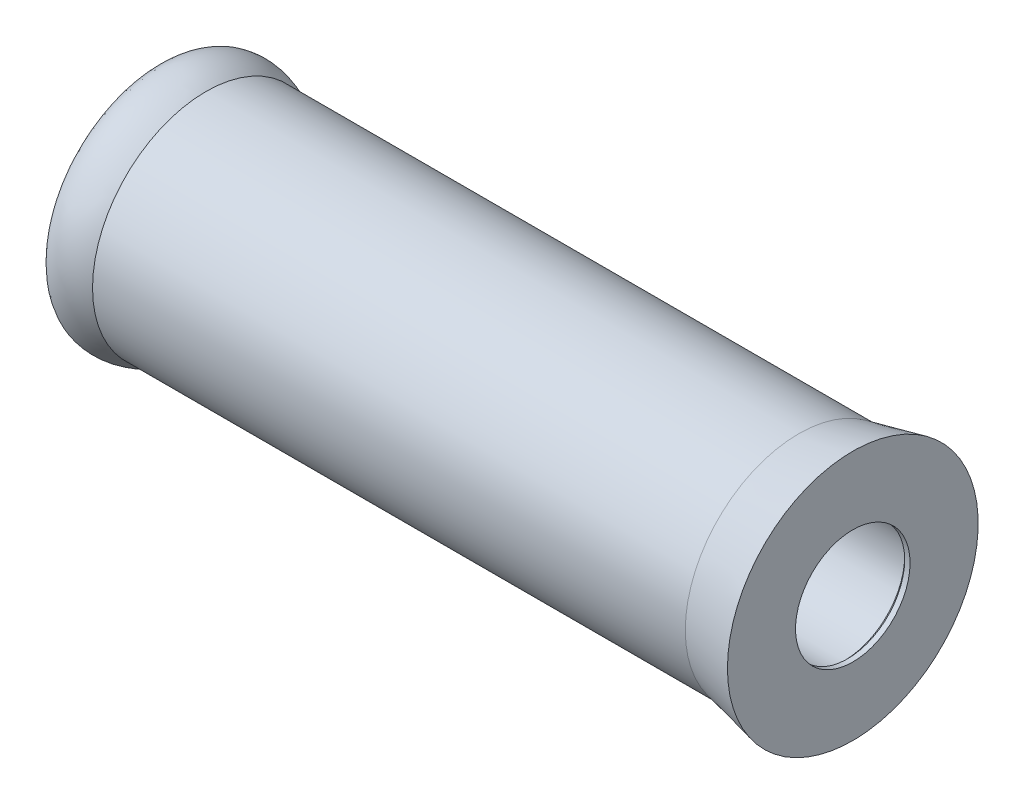
SolidWorks part; units mm, degrees
ref_plane "Front Plane" through (0, 0, 0) normal (0, 0, 1) x (1, 0, 0)
ref_plane "Top Plane" through (0, 0, 0) normal (0, 1, 0) x (1, 0, 0)
ref_plane "Right Plane" through (0, 0, 0) normal (1, 0, 0) x (0, 0, -1)
sketch "Sketch1" plane through (0, 0, 0) normal (1, 0, 0) x (0, 0, -1)
  circle A0 centre (0, 0) radius 11.2
  circle A1 centre (0, 0) radius 13.5
  dimension "D1" = 22.4
  dimension "D2" = 27
extrude "Boss-Extrude1" add sketch "Sketch1" along normal blind 60
ref_axis "Axis1" through (0, 0, 0) along (1, 0, 0)
sketch "Sketch2" plane through (0, 0, 0) normal (0, 0, 1) x (1, 0, 0)
  line L0 (8, 12.6) -> (8, 9.6)
  line L1 (8, 9.6) -> (11, 9.6)
  line L2 (0, 13.5) -> (0, -13.5) construction
  arc A0 (8, 12.6) -> (11, 9.6) centre (8, 9.6) cw
  dimension "D1" = 3
  dimension "D2" = 12.6
  dimension "D3" = 8
revolve "Cut-Revolve1" cut sketch "Sketch2" angle 360 about L0
pattern_circular "CirPattern1" count 8 over 360 about axis through (60, 0, 0) along (-1, 0, 0) of "Cut-Revolve1" reverse direction yes
pattern_linear "LPattern1" count 3 spacing 20 along (1, 0, 0) of "CirPattern1"
fillet "Fillet1" radius 3 1 edges at (0, 0, -11.2)
sketch "Sketch3" plane through (0, 0, 0) normal (0, 0, 1) x (1, 0, 0)
  line L0 (0, 0) -> (130, 0) construction
  line L1 (10.3, 21) -> (120, 21)
  line L2 (120, 21) -> (130, 23.2)
  line L3 (130, 23.2) -> (130, 11.2)
  line L5 (130, 11.2) -> (60, 11.2)
  line L7 (60, 11.2) -> (60, 13.5)
  line L8 (60, 13.5) -> (0, 13.5)
  line L9 (31.8374, 8.5654) -> (-11.2374, 33.4346) construction
  line L10 (15.8707, 28.0017) -> (-9.1636, 16.328) construction
  line L11 (60, -13.5) -> (60, 13.5) construction
  line L12 (60, -11.2) -> (60, 11.2) construction
  line L13 (60, 11.2) -> (50.5377, 11.2) construction
  line L14 (0, 16.8301) -> (0, 10.1693) construction
  line L15 (0, 13.5) -> (0, -13.5) construction
  spline S0 degree 3 poles (0, 13.5) (0, 17.4) (0.7244, 20.8873) (4.5323, 22.7857) (7.7019, 22.5) (10.3, 21) knots 0 0 0 0 0.520343 0.620343 1 1 1 1
  point P19 (60, 11.2)
  dimension "D5" = 30
  dimension "D6" = 10
  dimension "D7" = 25
  dimension "D8" = 13
  dimension "D9" = 13
  dimension "D1" = 21
  dimension "D2" = 130
  dimension "D3" = 22
  dimension "D4" = 10.3
  dimension "D10" = 3
  dimension "D11" = 12
  dimension "D12" = 10
revolve "Revolve1" add sketch "Sketch3" angle 360 about L0
sketch "Sketch4" plane through (130, 0, 0) normal (1, 0, 0) x (0, 0, -1)
  circle A0 centre (0, 0) radius 11.2 construction
  circle A1 centre (0, 0) radius 11.2
  circle A3 centre (0, 0) radius 10.6
  dimension "D1" = 0.6
extrude "Boss-Extrude3" add sketch "Sketch4" against normal blind 1
chamfer "Chamfer1" distance 0.6 angle 45 1 edges at (129, 0, -11.2)
